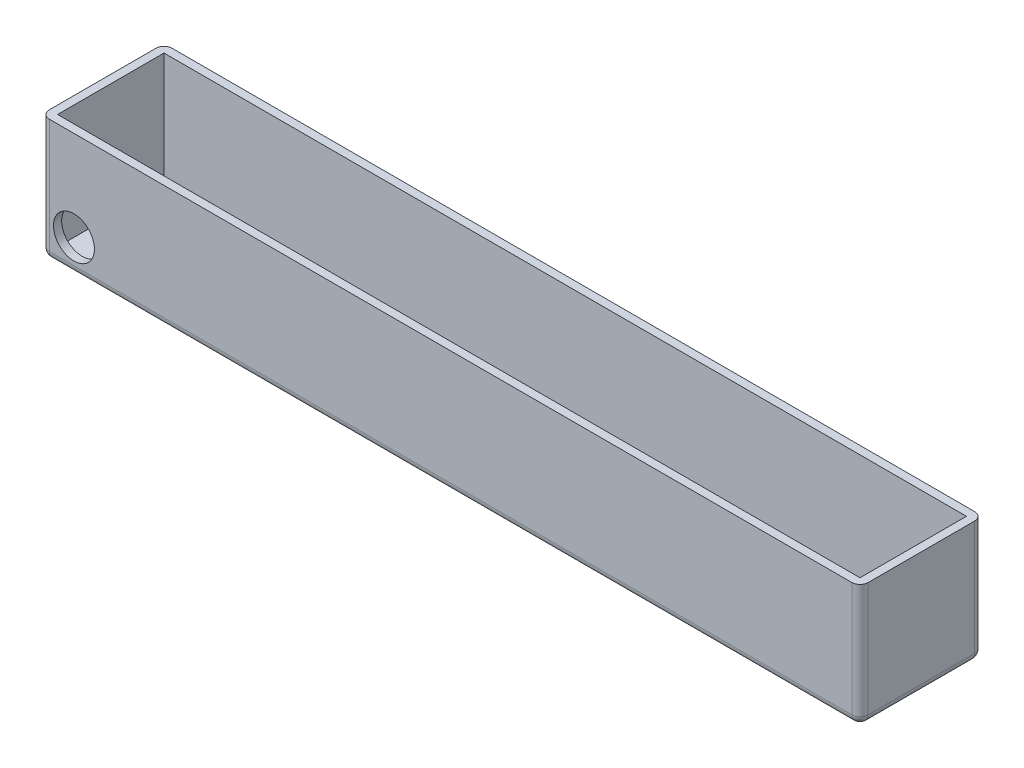
SolidWorks part; units mm, degrees
ref_plane "Front Plane" through (0, 0, 0) normal (0, 0, 1) x (1, 0, 0)
ref_plane "Top Plane" through (0, 0, 0) normal (0, 1, 0) x (1, 0, 0)
ref_plane "Right Plane" through (0, 0, 0) normal (1, 0, 0) x (0, 0, -1)
sketch "Sketch1" plane through (0, 0, 0) normal (1, 0, 0) x (0, 0, -1)
  line L0 (-19.05, 38.1) -> (-19.05, 2.54)
  line L1 (-16.51, 0) -> (16.51, 0)
  line L2 (-19.05, 38.1) -> (-16.51, 38.1)
  line L3 (-16.51, 38.1) -> (-16.51, 2.54)
  line L4 (-16.51, 2.54) -> (-6.35, 2.54)
  line L5 (-6.35, 2.54) -> (-6.35, 1.016)
  line L6 (-6.35, 1.016) -> (6.35, 1.016)
  line L8 (0, 1.016) -> (0, 0)
  line L9 (6.35, 2.54) -> (6.35, 1.016)
  line L10 (16.51, 2.54) -> (6.35, 2.54)
  line L11 (16.51, 38.1) -> (16.51, 2.54)
  line L12 (19.05, 38.1) -> (16.51, 38.1)
  line L13 (19.05, 38.1) -> (19.05, 2.54)
  arc A0 (-19.05, 2.54) -> (-16.51, 0) centre (-16.51, 2.54) ccw
  arc A1 (19.05, 2.54) -> (16.51, 0) centre (16.51, 2.54) cw
  point P13 (-19.05, 0)
  dimension "D7" = 2.54
  dimension "D1" = 19.05
  dimension "D2" = 12.7
  dimension "D4" = 38.1
  dimension "D5" = 1.524
extrude "Boss-Extrude1" add sketch "Sketch1" along normal mid plane 248.92 contours L0 A0 L1 L8 L6 L5 L4 L3 L2 | A1 L13 L12 L11 L10 L9 L6 L8 L1 region at (0, 37.674, 17.78) region at (0, 0.508, -0.426)
sketch "Sketch3" plane through (0, 0, 0) normal (1, 0, 0) x (0, 0, -1)
  line L0 (-19.05, 38.1) -> (-19.05, 2.54)
  line L1 (-16.51, 0) -> (16.51, 0)
  line L9 (-19.05, 38.1) -> (19.05, 38.1)
  line L10 (0, 38.1) -> (0, 0)
  line L11 (19.05, 38.1) -> (19.05, 2.54)
  arc A0 (-19.05, 2.54) -> (-16.51, 0) centre (-16.51, 2.54) ccw
  arc A1 (19.05, 2.54) -> (16.51, 0) centre (16.51, 2.54) cw
  dimension "D1" = 2.54
extrude "Boss-Extrude2" add sketch "Sketch3" along normal blind 2.54 from surface contours L0 A0 L1 L10 L9 | A1 L11 L9 L10 L1 region at (0, 19.0853, 9.5079) region at (0, 19.0853, -9.5079) starting at face at (124.46, 12.0443, 0)
extrude "Boss-Extrude3" add sketch "Sketch3<4>" against normal blind 2.54 from surface contours L0 A0 L1 L10 L9 | A1 L11 L9 L10 L1 region at (0, 19.0853, 9.5079) region at (0, 19.0853, -9.5079) starting at face at (-124.46, 12.0443, 0)
sketch "Sketch3<4>" plane through (0, 0, 0) normal (1, 0, 0) x (0, 0, -1) same geometry as "Sketch3"
sketch "Sketch4" plane through (0, 0, 0) normal (0, 0, 1) x (1, 0, 0)
  line L0 (127, 0) -> (-127, 0) construction
  line L1 (-127, 38.1) -> (-127, 2.54) construction
  circle A0 centre (-116.84, 10.16) radius 6.35
  dimension "D1" = 12.7
  dimension "D2" = 10.16
  dimension "D3" = 10.16
extrude "Cut-Extrude1" cut sketch "Sketch4" against normal up to surface (-16.51 mm away) from surface up to face at (0, 20.32, 16.51) starting at face at (0, 20.32, 19.05)
fillet "Fillet1" radius 2.54 5 edges at (-127, 20.32, 19.05) (-127, 0.7439, 18.3061) (-127, 20.32, -19.05) (-127, 0.7439, -18.3061) (-127, 0, 0)
fillet "Fillet2" radius 2.54 5 edges at (127, 20.32, -19.05) (127, 0.7439, -18.3061) (127, 20.32, 19.05) (127, 0.7439, 18.3061) (127, 0, 0)
